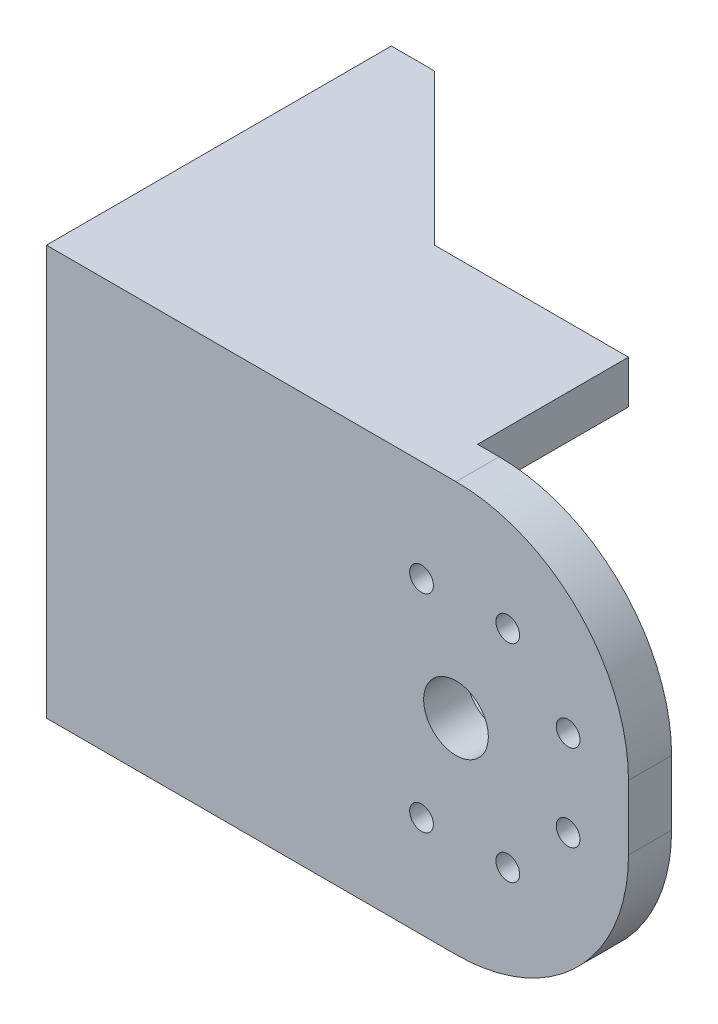
SolidWorks part; units mm, degrees
ref_plane "Front Plane" through (0, 0, 0) normal (0, 0, 1) x (1, 0, 0)
ref_plane "Top Plane" through (0, 0, 0) normal (0, 1, 0) x (1, 0, 0)
ref_plane "Right Plane" through (0, 0, 0) normal (1, 0, 0) x (0, 0, -1)
sketch "Sketch3" plane through (0, 0, 0) normal (0, 0, 1) x (1, 0, 0)
  line L6 (68.6171, 80.0599) -> (163.6171, 80.0599)
  line L10 (68.6171, 80.0599) -> (68.6171, -14.9401)
  line L36 (-101.4371, 49.8561) -> (-17.2351, 49.8561) construction
  line L70 (68.6171, -14.9401) -> (163.6171, -14.9401)
  line L71 (203.6171, 40.0599) -> (203.6171, 25.0599)
  circle A22 centre (163.6171, 32.5599) radius 7.5
  circle A23 centre (189.6171, 42.5599) radius 2.75
  circle A24 centre (155.6171, 56.5599) radius 2.75
  circle A25 centre (175.6171, 56.5599) radius 2.75
  circle A26 centre (155.6171, 8.5599) radius 2.75
  circle A27 centre (175.6171, 8.5599) radius 2.75
  circle A28 centre (189.6171, 22.5599) radius 2.75
  arc A29 (163.6171, -14.9401) -> (203.6171, 25.0599) centre (163.6171, 25.0599) ccw
  arc A30 (163.6171, 80.0599) -> (203.6171, 40.0599) centre (163.6171, 40.0599) cw
  point P23 (203.6171, 80.0599)
  dimension "D2" = 5.5
  dimension "D3" = 10
  dimension "D4" = 26
  dimension "D7" = 5.5
  dimension "D21" = 135
  dimension "D22" = 40
  dimension "D23" = 47.5
  dimension "D1" = 15
  dimension "D5" = 5.5
  dimension "D6" = 5.5
  dimension "D8" = 5.5
  dimension "D9" = 5.5
  dimension "D24" = 40
  dimension "D10" = 8
  dimension "D11" = 24
  dimension "D12" = 20
  dimension "D15" = 20
  dimension "D16" = 8
  dimension "D17" = 20
  dimension "D18" = 48
  dimension "D19" = 48
  dimension "D20" = 95
  dimension "D13" = 26
  dimension "D14" = 24
extrude "Boss-Extrude1" add sketch "Sketch3" along normal blind 10
sketch "Sketch4" plane through (0, 0, 0) normal (0, 0, -1) x (-1, 0, 0)
  line L0 (-68.6171, -14.9401) -> (-163.6171, -14.9401) construction
  line L1 (-68.6171, 80.0599) -> (-78.6171, 80.0599)
  line L2 (-68.6171, 80.0599) -> (-68.6171, -14.9401)
  line L3 (-68.6171, -14.9401) -> (-78.6171, -14.9401)
  line L4 (-78.6171, 80.0599) -> (-78.6171, -14.9401)
  dimension "D1" = 10
extrude "Boss-Extrude2" add sketch "Sketch4" along normal blind 70
sketch "Sketch5" plane through (0, 0, 0) normal (0, 0, -1) x (-1, 0, 0)
  line L1 (-78.6171, 80.0599) -> (-158.6171, 80.0599)
  line L2 (-78.6171, 80.0599) -> (-78.6171, 70.0599)
  line L3 (-78.6171, 70.0599) -> (-158.6171, 70.0599)
  line L4 (-158.6171, 80.0599) -> (-158.6171, 70.0599)
  line L5 (-78.6171, -14.9401) -> (-158.6171, -14.9401)
  line L6 (-78.6171, -14.9401) -> (-78.6171, -4.9401)
  line L7 (-78.6171, -4.9401) -> (-158.6171, -4.9401)
  line L8 (-158.6171, -14.9401) -> (-158.6171, -4.9401)
  dimension "D1" = 10
  dimension "D2" = 10
  dimension "D3" = 80
  dimension "D4" = 80
extrude "Boss-Extrude3" add sketch "Sketch5" along normal blind 35
sketch "Sketch6" plane through (0, -14.9401, 0) normal (0, -1, 0) x (1, 0, 0)
  line L0 (52.25, 0) -> (-52.25, 0) construction
  line L1 (88.6171, 0) -> (120.6171, 0)
  line L2 (88.6171, 0) -> (88.6171, -36)
  line L3 (88.6171, -36) -> (120.6171, -36)
  line L4 (120.6171, 0) -> (120.6171, -36)
  line L5 (68.6171, 10) -> (68.6171, -70) construction
  dimension "D1" = 20
  dimension "D2" = 36
  dimension "D3" = 32
extrude "Cut-Extrude1" [suppressed] cut sketch "Sketch6" against normal blind 43.8
fillet "Fillet2" [suppressed] radius 15
sketch "Sketch8" plane through (68.6171, 0, 0) normal (-1, 0, 0) x (0, 0, 1)
  line L0 (10, 80.0599) -> (-70, 80.0599) construction
  line L1 (-40, 32.5599) -> (-56.1679, 25.863) construction
  line L2 (-70, 32.5599) -> (0, 32.5599) construction
  line L3 (-70, -14.9401) -> (-70, 80.0599) construction
  circle A0 centre (-40, 32.5599) radius 7.5
  circle A1 centre (-56.1679, 25.863) radius 2.75
  circle A2 centre (-56.1679, 39.2569) radius 2.75
  circle A3 centre (-46.697, 48.7278) radius 2.75
  circle A4 centre (-33.303, 48.7278) radius 2.75
  circle A5 centre (-23.8321, 39.2569) radius 2.75
  circle A6 centre (-23.8321, 25.863) radius 2.75
  circle A7 centre (-33.303, 16.392) radius 2.75
  circle A8 centre (-46.697, 16.392) radius 2.75
  point P27 (-40, 32.5599)
  dimension "D1" = 15
  dimension "D6" = 5.5
  dimension "D2" = 47.5
  dimension "D3" = 30
  dimension "D4" = 17.5
  dimension "D5" = 22.5
  dimension "D7" = 8
extrude "Cut-Extrude2" cut sketch "Sketch8" against normal blind 43.8
fillet "Fillet3" [suppressed] radius 3
chamfer "Chamfer1" distance 35 angle 45 2 edges at (78.6171, 75.0599, -35) (78.6171, -9.9401, -35)
